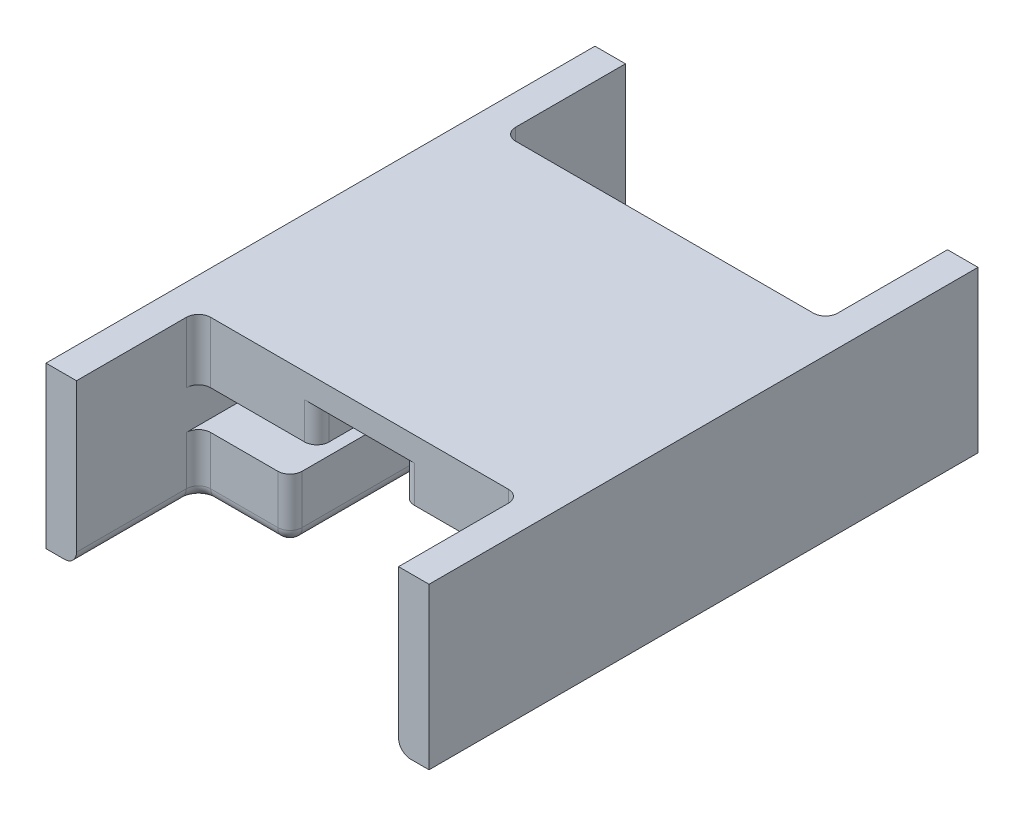
SolidWorks part; units mm, degrees
ref_plane "Front Plane" through (0, 0, 0) normal (0, 0, 1) x (1, 0, 0)
ref_plane "Top Plane" through (0, 0, 0) normal (0, 1, 0) x (1, 0, 0)
ref_plane "Right Plane" through (0, 0, 0) normal (1, 0, 0) x (0, 0, -1)
sketch "Sketch1" plane through (0, 0, 0) normal (0, 0, 1) x (1, 0, 0)
  line L1 (-35.5071, 8.5491) -> (-35.5071, -17.8009)
  line L2 (-35.5071, -17.8009) -> (-15.5071, -17.8009)
  line L3 (-15.5071, -17.8009) -> (-15.5071, -7.8009)
  line L4 (-15.5071, -7.8009) -> (-30.5071, -7.8009)
  line L5 (-30.5071, -7.8009) -> (-30.5071, -1.4509)
  line L6 (-30.5071, -1.4509) -> (-11.1071, -1.4509)
  line L7 (-4.1071, 8.5491) -> (-4.1071, -4.2151) construction
  line L8 (-35.5071, 8.5491) -> (27.2929, 8.5491)
  line L10 (2.8929, 4.5491) -> (-11.1071, 4.5491)
  line L11 (-11.1071, 4.5491) -> (-11.1071, -1.4509)
  line L12 (2.8929, 4.5491) -> (2.8929, -1.4509)
  line L13 (22.2929, -1.4509) -> (2.8929, -1.4509)
  line L14 (22.2929, -7.8009) -> (22.2929, -1.4509)
  line L15 (7.2929, -7.8009) -> (22.2929, -7.8009)
  line L16 (7.2929, -17.8009) -> (7.2929, -7.8009)
  line L17 (27.2929, -17.8009) -> (7.2929, -17.8009)
  line L18 (27.2929, 8.5491) -> (27.2929, -17.8009)
  point P2 (0, 0)
  dimension "D1" = 26.4
  dimension "D2" = 5
  dimension "D4" = 6.35
  dimension "D5" = 10
  dimension "D6" = 15
  dimension "D8" = 6
  dimension "D9" = 10
extrude "Boss-Extrude1" add sketch "Sketch1" against normal blind 50
ref_plane "Plane 1" through (0, 0, 0) normal (0, 0, 1) x (1, 0, 0)
sketch "Sketch2" plane through (0, 0, 0) normal (0, 0, 1) x (1, 0, 0)
  line L0 (-4.1071, 8.5491) -> (-4.1071, -1.4509) construction
  line L1 (-30.5071, -7.8009) -> (-30.5071, -1.4509) construction
  line L2 (-35.5071, 8.5491) -> (-30.5071, 8.5491)
  line L3 (-35.5071, 8.5491) -> (-35.5071, -17.8009)
  line L4 (-35.5071, -17.8009) -> (-30.5071, -17.8009)
  line L5 (-30.5071, 8.5491) -> (-30.5071, -17.8009)
  line L6 (-35.5071, 8.5491) -> (-35.5071, -17.8009) construction
  line L7 (27.2929, -17.8009) -> (22.2929, -17.8009)
  line L8 (22.2929, 8.5491) -> (22.2929, -17.8009)
  line L9 (27.2929, 8.5491) -> (22.2929, 8.5491)
  line L10 (27.2929, 8.5491) -> (27.2929, -17.8009)
  dimension "D1" = 0
  dimension "D2" = 0
extrude "Boss-Extrude2" add sketch "Sketch2" along normal blind 20 contours L3 L4 L5 L2 | L8 L7 L10 L9
ref_plane "Plane2" through (0, 0, -50) normal (0, 0, -1) x (-1, 0, 0)
sketch "Sketch4" plane through (0, 0, -50) normal (0, 0, -1) x (-1, 0, 0)
  line L0 (4.1071, 8.5491) -> (4.1071, -1.4509) construction
  line L21 (-27.2929, 8.5491) -> (-22.2929, 8.5491)
  line L22 (-27.2929, 8.5491) -> (-27.2929, -17.8009)
  line L23 (-27.2929, -17.8009) -> (-22.2929, -17.8009)
  line L24 (-22.2929, 8.5491) -> (-22.2929, -17.8009)
  line L25 (35.5071, 8.5491) -> (30.5071, 8.5491)
  line L26 (35.5071, 8.5491) -> (35.5071, -17.8009)
  line L27 (35.5071, -17.8009) -> (30.5071, -17.8009)
  line L28 (30.5071, 8.5491) -> (30.5071, -17.8009)
extrude "Boss-Extrude3" add sketch "Sketch4" along normal blind 20
fillet "Fillet2" radius 2 26 edges at (-30.5071, -12.8009, -50) (-30.5071, 3.5491, -50) (-30.5071, -17.8009, -60) (-30.5071, 3.5491, 0) (-30.5071, -17.8009, 10) (-23.0071, -17.8009, 0) (-15.5071, -12.8009, 0) (2.8929, 1.5491, 0) (-23.0071, -17.8009, -50) (-15.5071, -12.8009, -50) (2.8929, 1.5491, -50) (-15.5071, -17.8009, -25) (-30.5071, -12.8009, 0) (-11.1071, 1.5491, -50) (-11.1071, 1.5491, 0) (7.2929, -12.8009, -50) (7.2929, -17.8009, -25) (7.2929, -12.8009, 0) (22.2929, -17.8009, 10) (14.7929, -17.8009, 0) (22.2929, -12.8009, 0) (22.2929, 3.5491, 0) (22.2929, 3.5491, -50) (22.2929, -12.8009, -50) (22.2929, -17.8009, -60) (14.7929, -17.8009, -50)
